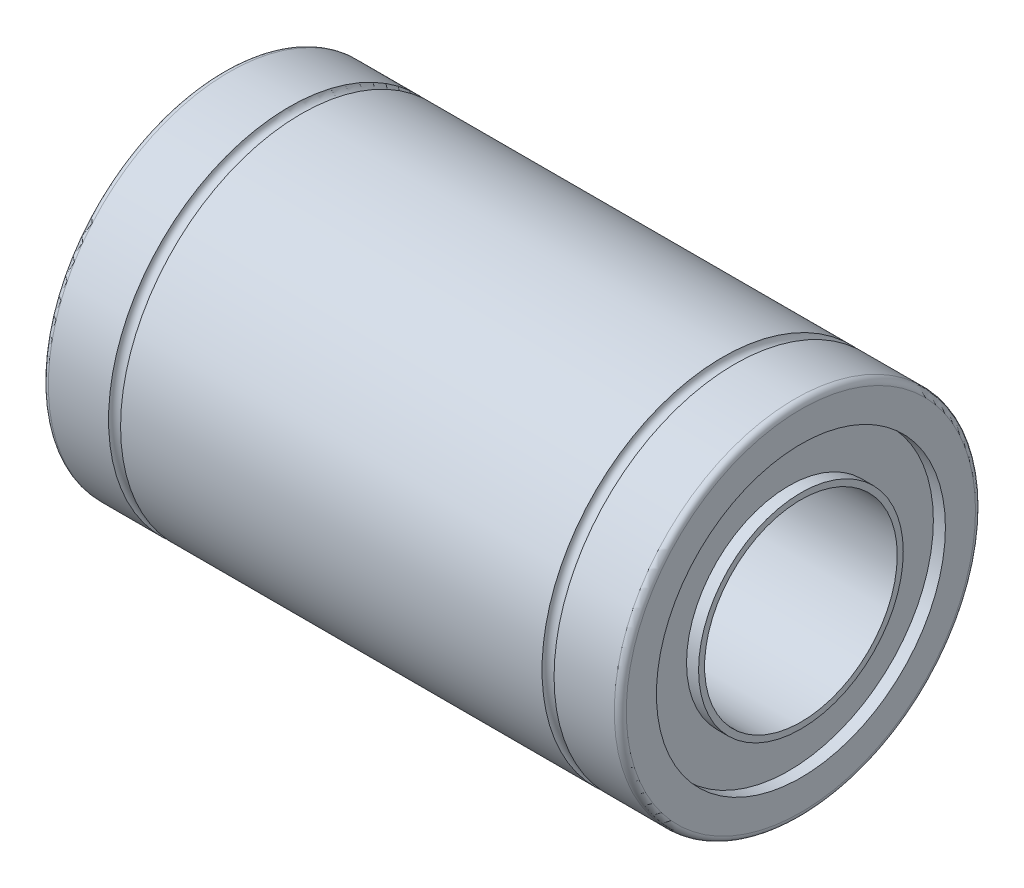
SolidWorks part; units mm, degrees
ref_plane "Front Plane" through (0, 0, 0) normal (0, 0, 1) x (1, 0, 0)
ref_plane "Top Plane" through (0, 0, 0) normal (0, 1, 0) x (1, 0, 0)
ref_plane "Right Plane" through (0, 0, 0) normal (1, 0, 0) x (0, 0, -1)
sketch "Sketch2" plane through (0, 0, 0) normal (1, 0, 0) x (0, 0, -1)
  circle A0 centre (0, 0) radius 6
  circle A1 centre (0, 0) radius 4
  circle A2 centre (0, 0) radius 7.5
  circle A3 centre (0, 0) radius 4.25
extrude "Extrude1" add sketch "Sketch2" along normal blind 12 and the other way blind 12 contours A2 A0 region at (0, 0, 7.2879)
extrude "Extrude2" add sketch "Sketch2<4>" along normal blind 12 and the other way blind 12 separate body contours A3 A1 region at (0, 0, 4.1298)
sketch "Sketch2<4>" plane through (0, 0, 0) normal (1, 0, 0) x (0, 0, -1) same geometry as "Sketch2"
extrude "Extrude3" add sketch "Sketch2<5>" along normal blind 11.5 and the other way blind 11.5 contours A0 A3 region at (0, 0, 5.8303)
sketch "Sketch2<5>" plane through (0, 0, 0) normal (1, 0, 0) x (0, 0, -1) same geometry as "Sketch2"
fillet "Fillet3" radius 0.25 1 edges at (12, 0, -7.5)
fillet "Fillet4" radius 0.25 1 edges at (-12, 0, -7.5)
ref_plane "Plane1" through (-9, 0, 0) normal (-1, 0, 0) x (0, 0, 1)
sketch "Sketch3" plane through (0, 0, 0) normal (0, 1, 0) x (1, 0, 0)
  line L0 (-9, 7.975) -> (-9, -7.975) construction
  line L1 (11.75, 7.5) -> (-11.75, 7.5) construction
  circle A0 centre (-9, 7.5) radius 0.25
sketch "Sketch4" plane through (-9, 0, 0) normal (-1, 0, 0) x (0, 0, 1)
  circle A0 centre (0, 0) radius 7.5
sweep "Cut-Sweep1" cut profiles "Sketch3" path "Sketch4"
ref_plane "Plane2" through (9, 0, 0) normal (1, 0, 0) x (0, 0, -1)
sketch "Sketch6" plane through (0, 0, 0) normal (0, 1, 0) x (1, 0, 0)
  line L0 (9, -7.975) -> (9, 7.975) construction
  circle A0 centre (9, 7.5) radius 0.25
sketch "Sketch7" plane through (9, 0, 0) normal (1, 0, 0) x (0, 0, -1)
  circle A0 centre (0, 0) radius 7.5
sweep "Cut-Sweep2" cut profiles "Sketch6" path "Sketch7"
